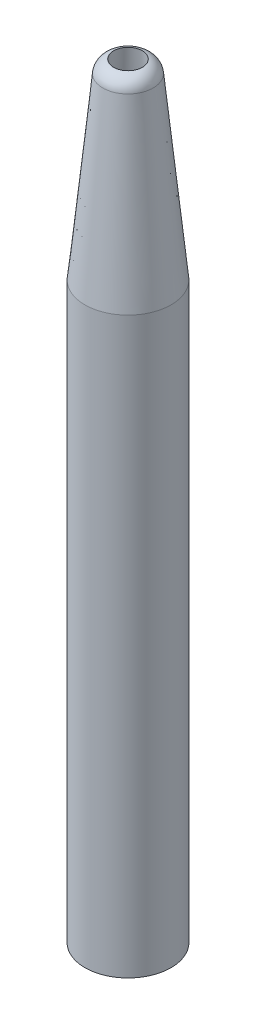
SolidWorks part; units mm, degrees
ref_plane "Front Plane" through (0, 0, 0) normal (0, 0, 1) x (1, 0, 0)
ref_plane "Top Plane" through (0, 0, 0) normal (0, 1, 0) x (1, 0, 0)
ref_plane "Right Plane" through (0, 0, 0) normal (1, 0, 0) x (0, 0, -1)
sketch "Sketch1" plane through (0, 0, 0) normal (0, 1, 0) x (1, 0, 0)
  circle A0 centre (0, 0) radius 9
  dimension "D1" = 18
extrude "Boss-Extrude1" add sketch "Sketch1" along normal blind 120
sketch "Sketch2" plane through (0, 0, 0) normal (0, -1, 0) x (1, 0, 0)
  circle A0 centre (0, 0) radius 7
  dimension "D1" = 14
extrude "Cut-Extrude1" cut sketch "Sketch2" against normal blind 120
sketch "Sketch3" plane through (0, 0, 0) normal (0, 0, 1) x (1, 0, 0)
  line L0 (9, 120) -> (5, 160)
  line L1 (5, 160) -> (3, 160)
  line L2 (3, 160) -> (7, 120)
  line L3 (9, 120) -> (-9, 120) construction
  line L4 (7, 120) -> (9, 120)
  dimension "D1" = 2
  dimension "D2" = 2
  dimension "D3" = 40
  dimension "D4" = 6
sketch "Sketch4" plane through (0, 0, 0) normal (0, 0, 1) x (1, 0, 0)
  line L0 (0, 0) -> (0, 167.2497) construction
revolve "Revolve1" add sketch "Sketch3" angle 360 about L0
fillet "Fillet5" radius 3 1 edges at (0, 160, -5)
fillet "Fillet6" radius 6 1 edges at (0, 0, -7)
